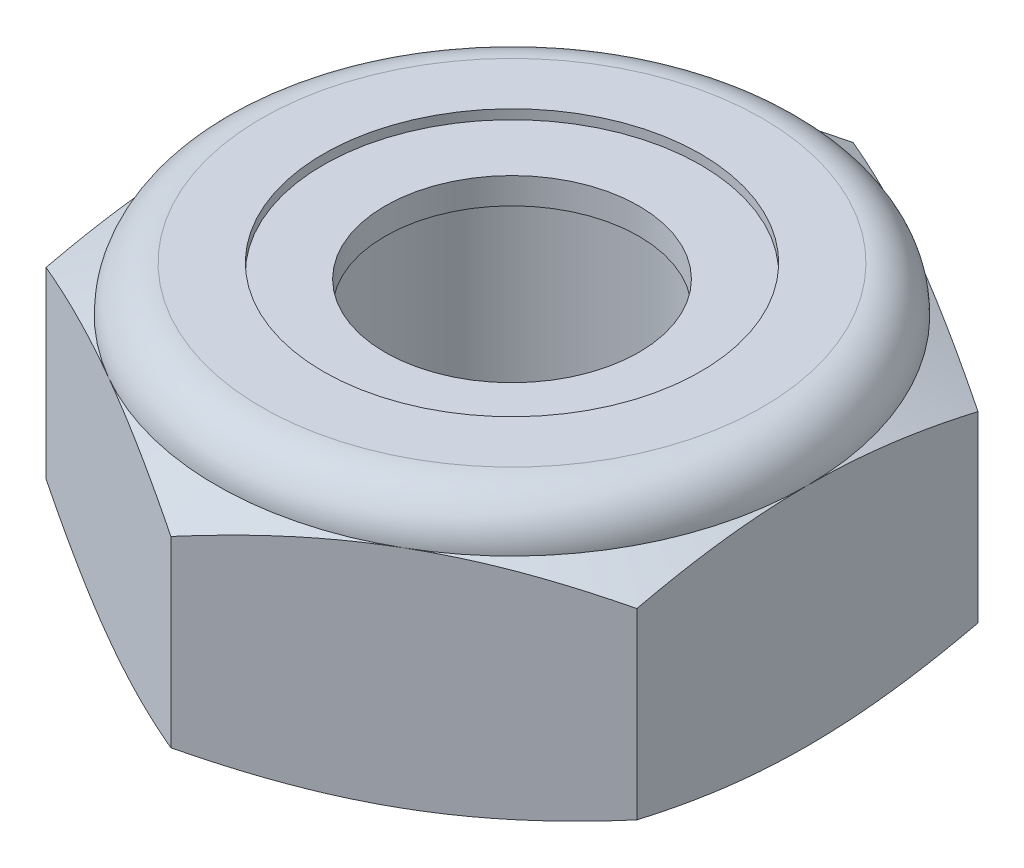
SolidWorks part; units mm, degrees
material "Plain Carbon Steel"
ref_plane "Front" through (0, 0, 0) normal (0, 0, 1) x (1, 0, 0)
ref_plane "Top" through (0, 0, 0) normal (0, 1, 0) x (1, 0, 0)
ref_plane "Right" through (0, 0, 0) normal (1, 0, 0) x (0, 0, -1)
sketch "Sketch1" plane through (0, 0, 0) normal (0, 1, 0) x (1, 0, 0)
  line L1 (0, 5.4993) -> (-4.7625, 2.7496)
  line L2 (-4.7625, 2.7496) -> (-4.7625, -2.7496)
  line L3 (-4.7625, -2.7496) -> (0, -5.4993)
  line L4 (0, -5.4993) -> (4.7625, -2.7496)
  line L5 (4.7625, -2.7496) -> (4.7625, 2.7496)
  line L6 (4.7625, 2.7496) -> (0, 5.4993)
  circle A0 centre (0, 0) radius 4.7625 construction
  dimension "Hex Flats" = 9.525
extrude "Extrude1" add sketch "Sketch1" along normal blind 4.3656
sketch "Sketch2" plane through (0, 0, 0) normal (1, 0, 0) x (0, 0, -1)
  line L0 (-2.413, 0) -> (-2.413, 4.3656) construction
  line L1 (0, 0) -> (2.413, 0)
  line L2 (0, 0) -> (0, 4.3656)
  line L3 (0, 4.3656) -> (2.413, 4.3656)
  line L4 (2.413, 0) -> (2.413, 4.3656)
  line L5 (-2.7496, 4.3656) -> (2.7496, 4.3656) construction
  line L7 (0, -2.413) -> (0, 0) construction
  dimension "Thread Dia" = 4.826
revolve "Revolve1" add sketch "Sketch2" angle 360 about L7
sketch "Sketch3" plane through (0, 0, 0) normal (1, 0, 0) x (0, 0, -1)
  line L0 (2.413, 4.3656) -> (-2.413, 4.3656) construction
  line L1 (-2.413, 4.3656) -> (-2.413, 3.5719) construction
  line L2 (-2.413, 3.5719) -> (2.413, 4.3656) construction
  line L3 (2.413, 4.3656) -> (2.4291, 4.2677) construction
  line L4 (2.4291, 4.2677) -> (2.5418, 3.5824)
  line L5 (2.5418, 3.5824) -> (2.0776, 3.7574)
  line L6 (2.0776, 3.7574) -> (2.0454, 3.9532)
  line L7 (2.0454, 3.9532) -> (2.4291, 4.2677)
  line L8 (2.0615, 3.8553) -> (2.4855, 3.9251) construction
  line L9 (2.413, 4.3656) -> (2.413, 3.9131) construction
  line L10 (2.413, 3.9131) -> (-2.413, 3.1194) construction
  line L11 (-2.413, 3.1194) -> (-2.413, 3.5719) construction
  line L12 (-0.1397, 4.3656) -> (0.1397, 2.6669) construction
  line L13 (-2.413, 0) -> (-2.413, 4.3656) construction
  line L14 (0, 4.3656) -> (2.413, 4.3656) construction
  line L15 (2.413, 0) -> (2.413, 4.3656) construction
  point P13 (0, 3.5163)
  dimension "D1" = 0.0992
  dimension "D2" = 0.1984
  dimension "D4" = 60
  dimension "D5" = 0.7937
sketch "Sketch4" plane through (0, 0, 0) normal (1, 0, 0) x (0, 0, -1)
  line L0 (0, 4.3656) -> (2.413, 4.3656)
  line L1 (2.413, 4.3656) -> (2.0454, 4.1942)
  line L2 (2.0454, 4.1942) -> (2.0454, 0.1714)
  line L3 (2.0454, 0.1714) -> (2.413, 0)
  line L4 (2.413, 0) -> (0, 0)
  line L5 (0, 0) -> (0, 4.3656)
  line L6 (2.413, 0) -> (2.413, 4.3656) construction
  line L7 (0, 4.3656) -> (2.413, 4.3656) construction
  line L8 (0, 0) -> (2.413, 0) construction
  line L9 (0, 0) -> (0, 4.3656) construction
  line L10 (0, 4.3656) -> (0, 4.7712) construction
  dimension "D1" = 25
combine bodies "Combine1" operation type subtract main body 108 bodies to subtract 109
sketch "Sketch5" plane through (0, 0, 0) normal (1, 0, 0) x (0, 0, -1)
  line L0 (0, 0) -> (4.7625, 0)
  line L1 (4.7625, 0) -> (5.4993, 0.3436)
  line L2 (5.4993, 0.3436) -> (5.4993, 3.2945)
  line L3 (5.4993, 3.2945) -> (4.7625, 3.638)
  line L4 (4.0349, 4.3656) -> (4.0349, 5.6356)
  line L5 (4.0349, 5.6356) -> (6.7693, 5.6356)
  line L6 (6.7693, 5.6356) -> (6.7693, -1.27)
  line L7 (6.7693, -1.27) -> (0, -1.27)
  line L8 (0, -1.27) -> (0, 0)
  line L9 (4.7625, 3.638) -> (4.7625, 0) construction
  line L10 (0, 0) -> (2.413, 0) construction
  line L13 (5.4993, 1.819) -> (6.7693, 1.819) construction
  line L14 (5.4993, 4.3656) -> (5.4993, 0) construction
  line L15 (0, 0) -> (0, 5.6356) construction
  line L20 (0, 5.6356) -> (4.0349, 5.6356) construction
  line L22 (0, 4.3656) -> (2.413, 4.3656) construction
  arc A0 (4.7625, 3.638) -> (4.0349, 4.3656) centre (4.0349, 3.638) ccw
  dimension "D1" = 25
  dimension "D2" = 1.27
  dimension "D4" = 0.9922
revolve "Cut-Revolve3" cut sketch "Sketch5" angle 360 about L15
sketch "Sketch6" plane through (0, 0, 0) normal (1, 0, 0) x (0, 0, -1)
  line L0 (0, 3.638) -> (4.6101, 3.638)
  line L1 (4.0349, 4.2132) -> (3.0402, 4.2132)
  line L2 (0, 5.6356) -> (0, 3.638)
  line L3 (3.0402, 5.6356) -> (0, 5.6356)
  line L4 (0, 5.6356) -> (4.0349, 5.6356) construction
  line L5 (0, 0) -> (0, 5.6356) construction
  line L6 (0, 5.6356) -> (0, 44.323) construction
  line L7 (3.0402, 4.2132) -> (3.0402, 5.6356)
  line L8 (4.0349, 4.3656) -> (4.0349, 4.2132) construction
  line L9 (3.0402, 4.2132) -> (2.0454, 4.2132) construction
  line L10 (2.0454, 4.2132) -> (2.0454, 4.1942) construction
  arc A0 (4.6101, 3.638) -> (4.0349, 4.2132) centre (4.0349, 3.638) ccw
  arc A1 (4.7625, 3.638) -> (4.0349, 4.3656) centre (4.0349, 3.638) ccw construction
  dimension "D1" = 0.1524
revolve "Cut-Revolve4" cut sketch "Sketch6" angle 360 about L6
sketch "Sketch7" plane through (0, 0, 0) normal (1, 0, 0) x (0, 0, -1)
  line L0 (2.0454, 3.7142) -> (4.528, 3.7142)
  line L1 (4.0349, 4.137) -> (2.0454, 4.137)
  line L2 (2.0454, 4.137) -> (2.0454, 3.7142)
  line L3 (2.0454, 3.7142) -> (0, 3.7142) construction
  line L4 (0, 3.7142) -> (0, 4.137) construction
  line L5 (0, 4.137) -> (2.0454, 4.137) construction
  line L6 (2.0454, 3.7142) -> (2.0454, 3.638) construction
  line L7 (0, 3.638) -> (4.6101, 3.638) construction
  line L8 (4.0349, 4.137) -> (4.0349, 4.2132) construction
  arc A0 (4.528, 3.7142) -> (4.0349, 4.137) centre (4.0349, 3.638) ccw
  arc A2 (4.6101, 3.638) -> (4.0349, 4.2132) centre (4.0349, 3.638) ccw construction
  dimension "D1" = 0.0762
revolve "Revolve2" add sketch "Sketch7" angle 360 about L4
ref_axis "Axis1" through (0, 0, 0) along (0, 1, 0)
equation "\"D1@Sketch3\"=\"Thread Pitch@Sketch3\"/8"
equation "\"D2@Sketch3\"=\"Thread Pitch@Sketch3\"/4"
equation "\"D5@Sketch3\"=\"Thread Pitch@Sketch3\""
equation "\"D4@Sketch5\"=\"Height@Extrude1\"/6"
